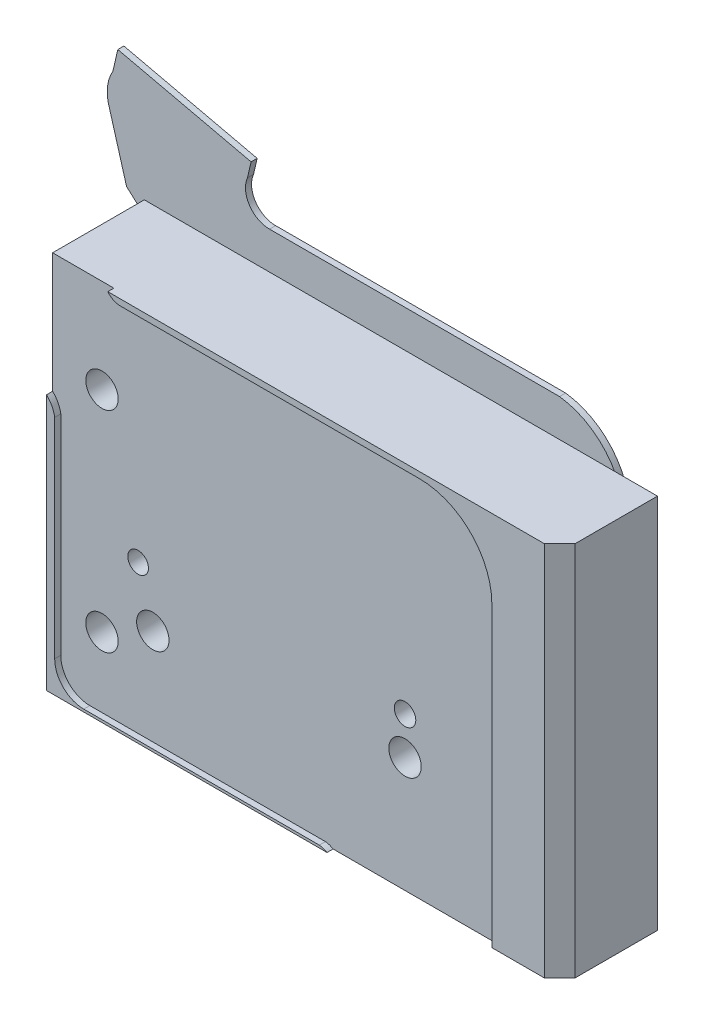
SolidWorks part; units mm, degrees
ref_plane "Alzado" through (0, 0, 0) normal (0, 0, 1) x (1, 0, 0)
ref_plane "Planta" through (0, 0, 0) normal (0, 1, 0) x (1, 0, 0)
ref_plane "Vista lateral" through (0, 0, 0) normal (1, 0, 0) x (0, 0, -1)
sketch "Croquis1" plane through (0, 0, 0) normal (0, 0, 1) x (1, 0, 0)
  line L0 (2788.5159, 1163.0629) -> (2845.3203, 1163.0629)
  line L1 (2857.8614, 1148.5546) -> (2857.8614, 1105.8847)
  line L2 (2857.8614, 1105.8847) -> (2859.7096, 1099.9695)
  line L3 (2859.7096, 1099.9695) -> (2859.7096, 1086.6685)
  line L4 (2859.7096, 1086.6685) -> (2831.925, 1086.6685)
  line L5 (2831.925, 1090.237) -> (2831.925, 1086.6685)
  line L6 (2781.0738, 1094.0948) -> (2827.4673, 1094.0948)
  line L7 (2777.0773, 1099.7185) -> (2777.0773, 1139.3578)
  line L8 (2774.3125, 1143.942) -> (2760.5085, 1156.2703)
  line L9 (2760.5085, 1156.2703) -> (2756.8696, 1168.8846)
  line L10 (2757.8278, 1174.4924) -> (2758.7888, 1178.6707)
  line L11 (2784.8931, 1172.6668) -> (2784.1913, 1169.6153)
  line L12 (2784.8931, 1172.6668) -> (2758.7888, 1178.6707)
  line L13 (2783.6509, 1147.3752) -> (2783.6509, 1106.2537) construction
  arc A0 (2857.8614, 1148.5546) -> (2845.3203, 1163.0629) centre (2843.5531, 1148.8609) ccw
  arc A5 (2831.925, 1090.237) -> (2827.4673, 1094.0948) centre (2827.128, 1089.1983) ccw
  arc A6 (2777.0773, 1099.7185) -> (2781.0738, 1094.0948) centre (2782.0012, 1098.9858) ccw
  arc A7 (2777.0773, 1139.3578) -> (2774.3125, 1143.942) centre (2770.304, 1138.3986) ccw
  arc A8 (2757.8278, 1174.4924) -> (2756.8696, 1168.8846) centre (2764.6187, 1170.4463) ccw
  arc A15 (2784.1913, 1169.6153) -> (2788.5159, 1163.0629) centre (2788.4536, 1167.7251) ccw
  circle A16 centre (2819.6018, 1133.2354) radius 4.4305
  circle A17 centre (2790.7272, 1121.6381) radius 2.0215
  circle A18 centre (2783.6509, 1147.3752) radius 2.8722
  circle A19 centre (2793.6078, 1111.4193) radius 2.6807
  circle A20 centre (2783.6509, 1106.2537) radius 2.8722
  circle A22 centre (2842.9135, 1132.266) radius 2.7764
  circle A23 centre (2843.0093, 1122.0339) radius 2.1062
  circle A24 centre (2843.0093, 1114.6706) radius 2.7904
  point P0 (0, 0)
  dimension "D1" = 14.8521
extrude "Saliente-Extruir1" add sketch "Croquis1" along normal blind 1.19
ref_plane "Plano1" through (0, 0, 11.19) normal (0, 0, 1) x (1, 0, 0)
sketch "Croquis7" plane through (0, 0, 11.19) normal (0, 0, 1) x (1, 0, 0)
  line L0 (2777.0773, 1139.3578) -> (2777.0773, 1099.7185) construction
  line L1 (2771.9773, 1090.0948) -> (2874.4973, 1090.0948)
  line L2 (2771.9773, 1090.0948) -> (2771.9773, 1167.7648)
  line L3 (2771.9773, 1167.7648) -> (2874.4973, 1167.7648)
  line L4 (2874.4973, 1090.0948) -> (2874.4973, 1167.7648)
  line L5 (2781.0738, 1094.0948) -> (2827.4673, 1094.0948) construction
  dimension "D1" = 102.52
  dimension "D2" = 77.67
  dimension "D3" = 5.1
  dimension "D4" = 4
extrude "Saliente-Extruir2" add sketch "Croquis7" along normal blind 19.15 separate body
sketch "Croquis8" plane through (0, 0, 11.19) normal (0, 0, -1) x (-1, 0, 0)
  circle A0 centre (-2783.6509, 1106.2537) radius 2.8561
  circle A1 centre (-2783.6509, 1147.3752) radius 2.8722
  circle A2 centre (-2790.7272, 1121.6381) radius 2.0215
  circle A3 centre (-2793.6078, 1111.4193) radius 3.175
  circle A4 centre (-2819.6018, 1133.2354) radius 4.4305
  circle A5 centre (-2842.9135, 1132.266) radius 2.7764
  circle A6 centre (-2843.0093, 1122.0339) radius 2.1062
  circle A7 centre (-2843.0093, 1114.6706) radius 3.175
  dimension "D1" = 6.35
extrude "Cortar-Extruir3" cut sketch "Croquis8" against normal through all contours A2 | A6 | A7 | A3
extrude "Cortar-Extruir4" cut sketch "Croquis8<7>" against normal up to surface (19.15 mm away) contours A1 | A0 up to face at (2790.4328, 1111.4193, 30.34)
sketch "Croquis8<7>" plane through (0, 0, 11.19) normal (0, 0, -1) x (-1, 0, 0) same geometry as "Croquis8"
sketch "Croquis12" plane through (0, 0, 11.19) normal (0, 0, -1) x (-1, 0, 0)
  circle A0 centre (-2783.6509, 1147.3752) radius 2.8722
  circle A1 centre (-2783.6509, 1106.2537) radius 2.8561
extrude "Saliente-Extruir3" add sketch "Croquis12" against normal blind 7
sketch "Croquis13" plane through (0, 0, 30.34) normal (0, 0, 1) x (1, 0, 0)
  line L0 (2859.7096, 1090.0948) -> (2859.7096, 1150.3629)
  line L1 (2859.7096, 1099.9695) -> (2859.7096, 1086.6685) construction
  line L2 (2771.9773, 1090.0948) -> (2874.4973, 1090.0948) construction
  line L3 (2847.0096, 1163.0629) -> (2788.5159, 1163.0629)
  line L4 (2859.7096, 1090.0948) -> (2831.9536, 1090.0948)
  line L5 (2827.4673, 1094.0948) -> (2781.2673, 1094.0948)
  line L6 (2777.0773, 1098.2848) -> (2777.0773, 1139.3578)
  line L7 (2783.7912, 1167.7648) -> (2771.9773, 1167.7648)
  line L8 (2771.9773, 1167.7648) -> (2771.9773, 1146.0275)
  line L9 (2774.3125, 1143.942) -> (2760.5085, 1156.2703) construction
  line L10 (2771.9773, 1146.0275) -> (2774.3125, 1143.942)
  line L11 (2874.4973, 1167.7648) -> (2771.9773, 1167.7648) construction
  line L12 (2771.9773, 1090.0948) -> (2874.4973, 1090.0948) construction
  line L13 (2847.0096, 1164.5629) -> (2788.5049, 1164.5629)
  line L14 (2785.6911, 1169.2648) -> (2770.4773, 1169.2648)
  line L15 (2770.4773, 1169.2648) -> (2770.4773, 1145.356)
  line L16 (2770.4773, 1145.356) -> (2773.3745, 1142.7686)
  line L17 (2775.5773, 1098.2848) -> (2775.5773, 1139.2455)
  line L18 (2827.4107, 1092.5948) -> (2781.2673, 1092.5948)
  line L19 (2861.2096, 1088.5948) -> (2830.4823, 1088.5948)
  line L20 (2861.2096, 1088.5948) -> (2861.2096, 1150.3629)
  arc A0 (2831.9536, 1090.0948) -> (2827.4673, 1094.0948) centre (2827.128, 1089.1983) ccw
  arc A1 (2788.5159, 1163.0629) -> (2783.7912, 1167.7648) centre (2788.4536, 1167.7251) cw
  arc A2 (2784.1913, 1169.6153) -> (2788.5159, 1163.0629) centre (2788.4536, 1167.7251) ccw construction
  arc A3 (2774.3125, 1143.942) -> (2777.0773, 1139.3578) centre (2770.304, 1138.3986) cw
  arc A4 (2777.0773, 1139.3578) -> (2774.3125, 1143.942) centre (2770.304, 1138.3986) ccw construction
  arc A5 (2831.925, 1090.237) -> (2827.4673, 1094.0948) centre (2827.128, 1089.1983) ccw construction
  arc A6 (2781.2673, 1094.0948) -> (2777.0773, 1098.2848) centre (2781.2673, 1098.2848) cw
  arc A7 (2859.7096, 1150.3629) -> (2847.0096, 1163.0629) centre (2847.0096, 1150.3629) ccw
  arc A8 (2788.5049, 1164.5629) -> (2785.6911, 1169.2648) centre (2788.4536, 1167.7251) cw
  arc A9 (2773.3745, 1142.7686) -> (2775.5773, 1139.2455) centre (2770.304, 1138.3986) cw
  arc A10 (2781.2673, 1092.5948) -> (2775.5773, 1098.2848) centre (2781.2673, 1098.2848) cw
  arc A11 (2830.4823, 1088.5948) -> (2827.4107, 1092.5948) centre (2827.128, 1089.1983) ccw
  arc A12 (2861.2096, 1150.3629) -> (2847.0096, 1164.5629) centre (2847.0096, 1150.3629) ccw
  circle M12 centre (2783.6509, 1147.3752) radius 2.8722
  circle M13 centre (2783.6509, 1106.2537) radius 2.8561
  circle M14 centre (2793.6078, 1111.4193) radius 3.175
  circle M15 centre (2843.0093, 1114.6706) radius 3.175
  circle M16 centre (2843.0093, 1122.0339) radius 2.1062
  circle M17 centre (2790.7272, 1121.6381) radius 2.0215
  line M18 (2771.9773, 1167.7648) -> (2771.9773, 1090.0948)
  line M19 (2771.9773, 1090.0948) -> (2874.4973, 1090.0948)
  line M21 (2874.4973, 1167.7648) -> (2771.9773, 1167.7648)
  dimension "D1" = 4.19
  dimension "D2" = 12.7
  dimension "D3" = 1.5
extrude "Cortar-Extruir8" cut sketch "Croquis13" against normal blind 1.19 contours L0 A7 L3 A1 L10 A3 L6 A6 L5 A0 M21 M18 M19 M12 M14 M16 M17 M15 M13 | L20 A12 L13 A8 A1 L3 A7 L0 M21 M19 | A11 A0 L5 A6 L6 A3 L10 L16 A9 L17 A10 L18 M19 M18 region at (2817.8717, 1128.7041, 30.34) region at (2860.8062, 1120.2288, 30.34) region at (2831.1849, 1090.9149, 30.34)
sketch "Croquis14" plane through (0, 0, 11.19) normal (0, 0, -1) x (-1, 0, 0)
  line L0 (-2773.9773, 1092.0948) -> (-2874.4973, 1092.0948)
  line L1 (-2771.9773, 1167.7648) -> (-2874.4973, 1167.7648)
  line L2 (-2771.9773, 1167.7648) -> (-2771.9773, 1090.0948)
  line L3 (-2771.9773, 1090.0948) -> (-2874.4973, 1090.0948)
  line L4 (-2874.4973, 1167.7648) -> (-2874.4973, 1090.0948)
  line L5 (-2773.9773, 1165.7648) -> (-2773.9773, 1092.0948)
  line L6 (-2773.9773, 1165.7648) -> (-2874.4973, 1165.7648)
  line M9 (-2771.9773, 1090.0948) -> (-2771.9773, 1167.7648)
  line M10 (-2771.9773, 1167.7648) -> (-2874.4973, 1167.7648)
  line M11 (-2874.4973, 1167.7648) -> (-2874.4973, 1090.0948)
  line M12 (-2874.4973, 1090.0948) -> (-2771.9773, 1090.0948)
  dimension "D1" = 2
extrude "Cortar-Extruir9" cut sketch "Croquis14" against normal through all contours L6 L5 L0 M11 M12 M9 M10 region at (2772.6911, 1128.9298, 11.19)
sketch "Croquis15" plane through (0, 0, 29.15) normal (0, 0, 1) x (1, 0, 0)
  circle A0 centre (2783.6509, 1147.3752) radius 3.175
  circle A1 centre (2783.6509, 1106.2537) radius 3.175
  dimension "D1" = 6.35
extrude "Cortar-Extruir10" cut sketch "Croquis15" against normal up to surface (10.96 mm away) up to face at (2780.7948, 1106.2537, 18.19)
chamfer "Chaflán1" distance 3 angle 45 1 edges at (2874.4973, 1128.9298, 30.34)
